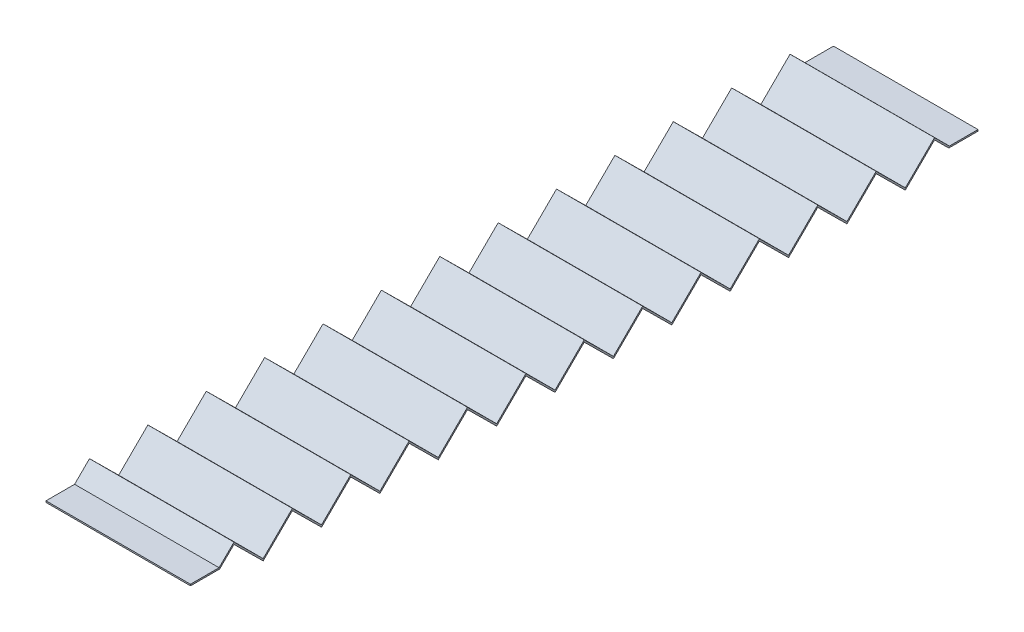
SolidWorks part; units mm, degrees
ref_plane "Front Plane" through (0, 0, 0) normal (0, 0, 1) x (1, 0, 0)
ref_plane "Top Plane" through (0, 0, 0) normal (0, 1, 0) x (1, 0, 0)
ref_plane "Right Plane" through (0, 0, 0) normal (1, 0, 0) x (0, 0, -1)
sketch "Sketch2" plane through (0, 0, 0) normal (0, 0, 1) x (1, 0, 0)
  line L1 (-27.5, 10) -> (27.5, 10)
  line L2 (-27.5, 10) -> (-27.5, 0)
  line L3 (-27.5, 0) -> (27.5, 0)
  line L4 (27.5, 10) -> (27.5, 0)
  point P4 (0, 0)
  dimension "D1" = 10
  dimension "D2" = 55
sketch "Sketch3" plane through (0, 0, 0) normal (1, 0, 0) x (0, 0, -1)
  line L0 (0, 10) -> (272.53, 10) construction
  line L1 (0, 0) -> (272.53, 0) construction
  line L3 (10, 5) -> (15.0506, 10)
  line L4 (15.0506, 10) -> (25.1518, 0)
  line L5 (25.1518, 0) -> (35.253, 10)
  line L6 (35.253, 10) -> (45.3542, 0)
  line L7 (45.3542, 0) -> (55.4554, 10)
  line L8 (55.4554, 10) -> (65.5566, 0)
  line L9 (65.5566, 0) -> (75.6578, 10)
  line L10 (75.6578, 10) -> (85.759, 0)
  line L11 (85.759, 0) -> (95.8602, 10)
  line L12 (95.8602, 10) -> (105.9614, 0)
  line L13 (105.9614, 0) -> (116.0626, 10)
  line L14 (116.0626, 10) -> (126.1638, 0)
  line L15 (126.1638, 0) -> (136.265, 10)
  line L16 (136.265, 10) -> (146.3662, 0)
  line L17 (146.3662, 0) -> (156.4674, 10)
  line L18 (156.4674, 10) -> (166.5686, 0)
  line L19 (0, 10) -> (0, 0) construction
  line L20 (166.5686, 0) -> (176.6698, 10)
  line L21 (176.6698, 10) -> (186.771, 0)
  line L22 (186.771, 0) -> (196.8722, 10)
  line L23 (196.8722, 10) -> (206.9734, 0)
  line L24 (206.9734, 0) -> (217.0746, 10)
  line L25 (217.0746, 10) -> (227.1758, 0)
  line L26 (227.1758, 0) -> (237.277, 10)
  line L27 (237.277, 10) -> (247.3782, 0)
  line L28 (247.3782, 0) -> (257.4794, 10)
  line L29 (257.4794, 10) -> (262.53, 5)
  line L30 (272.53, 10) -> (272.53, 0) construction
  line L31 (10, 5) -> (0, 5)
  line L32 (262.53, 5) -> (272.53, 5)
  line L33 (272.53, -12.3958) -> (272.53, -19.8536) construction
  dimension "D2" = 10
  dimension "D1" = 10
  dimension "D3" = 10
extrude "Extrude-Thin1" add sketch "Sketch3" against normal mid plane 50 thin thin type mid plane wall 0.5
